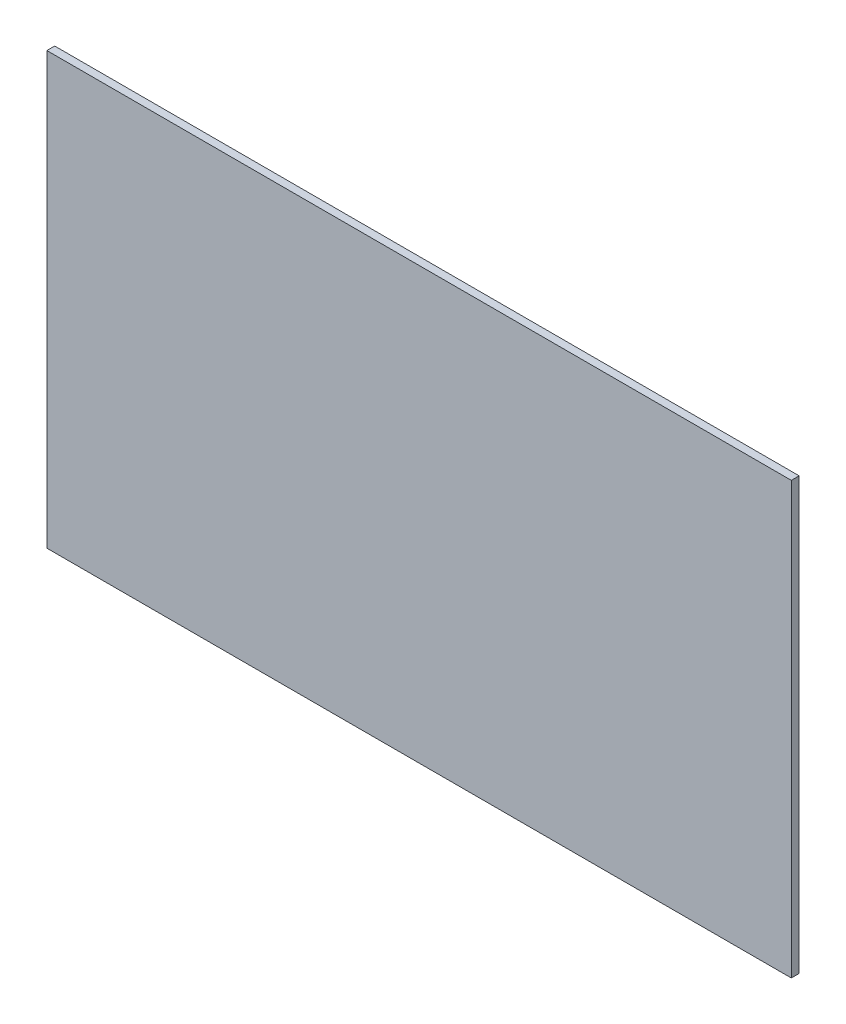
SolidWorks part; units mm, degrees
ref_plane "Plan de face" through (0, 0, 0) normal (0, 0, 1) x (1, 0, 0)
ref_plane "Plan de dessus" through (0, 0, 0) normal (0, 1, 0) x (1, 0, 0)
ref_plane "Plan de droite" through (0, 0, 0) normal (1, 0, 0) x (0, 0, -1)
sketch "Esquisse1" plane through (0, 0, 0) normal (0, 0, 1) x (1, 0, 0)
  line L1 (-189.6573, 78.6929) -> (190.3427, 78.6929)
  line L2 (-189.6573, 78.6929) -> (-189.6573, -141.3071)
  line L3 (-189.6573, -141.3071) -> (190.3427, -141.3071)
  line L4 (190.3427, 78.6929) -> (190.3427, -141.3071)
  dimension "D1" = 380
  dimension "D2" = 220
extrude "Boss.-Extru.1" add sketch "Esquisse1" along normal blind 4
